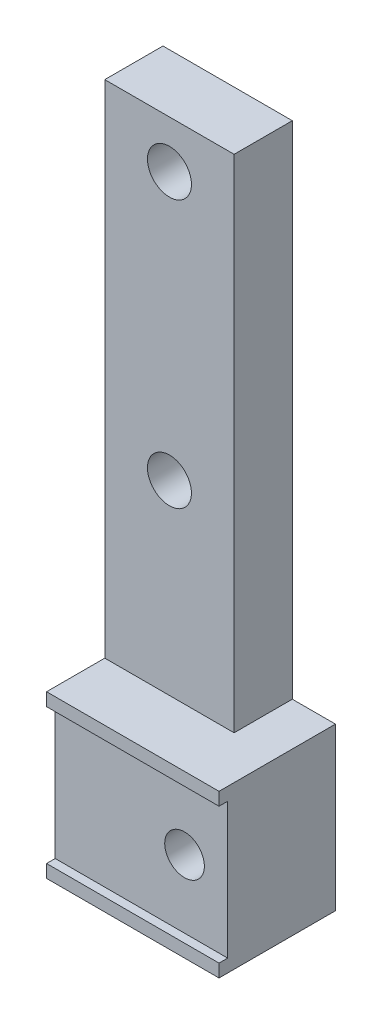
SolidWorks part; units mm, degrees
ref_plane "Front Plane" through (0, 0, 0) normal (0, 0, 1) x (1, 0, 0)
ref_plane "Top Plane" through (0, 0, 0) normal (0, 1, 0) x (1, 0, 0)
ref_plane "Right Plane" through (0, 0, 0) normal (1, 0, 0) x (0, 0, -1)
sketch "ProfileSketch3" plane through (0, 0, 0) normal (0, 0, 1) x (1, 0, 0)
  line L1 (0, 0) -> (20, 0)
  line L2 (0, 0) -> (0, 76.85)
  line L4 (20, 0) -> (20, 18.75)
  line L8 (0, 76.85) -> (15, 76.85)
  line L9 (15, 76.85) -> (15, 18.75)
  line L10 (15, 18.75) -> (20, 18.75)
  circle A0 centre (7.5, 40.35) radius 2.55
  circle A1 centre (7.5, 71.35) radius 2.55
  circle A3 centre (15, 9.375) radius 2.3
  dimension "D8" = 5.1
  dimension "D12" = 4.6
  dimension "D6" = 20
  dimension "D5" = 5.5
  dimension "D3" = 31
  dimension "D13" = 5
  dimension "D15" = 9.375
  dimension "D2" = 7.5
  dimension "D4" = 76.85
  dimension "D7" = 15
  dimension "D9" = 18.75
extrude "ProfileBoss-Extrude1" add sketch "ProfileSketch3" along normal blind 13.5
sketch "Sketch1" plane through (0, 0, 13.5) normal (0, 0, 1) x (1, 0, 0)
  line L0 (0, 76.85) -> (0, 0) construction
  line L1 (0, 1.5) -> (20, 1.5)
  line L2 (0, 1.5) -> (0, 17.25)
  line L3 (0, 17.25) -> (20, 17.25)
  line L4 (20, 1.5) -> (20, 17.25)
  line L5 (20, 0) -> (20, 18.75) construction
  line L6 (0, 0) -> (20, 0) construction
  dimension "D1" = 1.5
  dimension "D2" = 15.75
  dimension "D3" = 7.875
  dimension "D4" = 7.875
extrude "SlidingMountCut-Extrude1" cut sketch "Sketch1" against normal blind 1
sketch "Sketch2" plane through (0, 0, 13.5) normal (0, 0, 1) x (1, 0, 0)
  line L1 (0, 76.85) -> (15, 76.85)
  line L2 (0, 76.85) -> (0, 18.75)
  line L3 (0, 18.75) -> (15, 18.75)
  line L4 (15, 76.85) -> (15, 18.75)
extrude "Cut-Extrude1" cut sketch "Sketch2" against normal blind 6.75
equation "\"SK8RodShaftSupportHeight\"= 42mm"
equation "\"SK8RodShaftSupportLength\"= 15mm"
equation "\"SK8MountHoleDiameter\"= 5mm + .1mm'Add .1mm for printing"
equation "\"SK8RiserWidth\"= 6.75mm'Measured to meet Nema17 Mount Hole Center axis"
equation "\"SK8MountHoleFromSide\"= \"SK8RodShaftSupportLength\" / 2"
equation "\"SK8MountHoleFromEitherEnd\"= 5.5mm"
equation "\"MicroSwitchCutOutLength\"= 13.05mm"
equation "\"MicroSwitchHeight\"= 6.55mm"
equation "\"MicroSwitchMountingHoleOffsetFromSide\"= 3.35mm"
equation "\"MicroSwitchTerminalHeight\"= 3.5mm"
equation "\"MicroSwitchExtraMountingHeight\"= 2mm"
equation "\"MicroSwitchDepth\"= 2.8mm"
equation "\"MicroSwitchMountingHoleOffsetFromBottom\"= 7mm"
equation "\"M2HeatInsertHoleDiameter\"= 3mm + .1mm'Add .1mm for printing"
equation "\"M2HeatInsertHoleDepth\"= 3.1mm'Spec"
equation "\"D1@ProfileBoss-Extrude1\"=\"YAxisHolderThickness\" * 2"
equation "\"MicroSwitchCutOutHeight\"= \"MicroSwitchExtraMountingHeight\" + \"MicroSwitchTerminalHeight\" + \"MicroSwitchHeight\""
equation "\"EndStopCableWidth\"= 3.75mm"
equation "\"EndStopCableDepth\"= 1.75mm"
equation "\"D6@ProfileSketch3\"= \"YEndStopHolderLength\""
equation "\"D5@ProfileSketch3\"=\"SK8MountHoleFromEitherEnd\""
equation "\"D8@ProfileSketch3\"=\"SK8MountHoleDiameter\""
equation "\"Nema17StepperMountSlotDistance\"=31"
equation "\"D3@ProfileSketch3\"=\"Nema17StepperMountSlotDistance\""
equation "\"M3HeatInsertDiameter\"=4.6"
equation "\"YAxisHolderThickness\"= \"SK8RiserWidth\""
equation "\"YEndStopHolderLength\"= \"SK8RodShaftSupportLength\" + \"YEndStopBaseExtraLength\""
equation "\"YEndStopBaseExtraLength\"= 5mm"
equation "\"M3HeatInsertHoleDepth\"= 5.5mm"
equation "\"YAxisEndStopMicroSwitchHolderHeight\"= 18.75'Same as XAxisMircoSwitchHolder"
equation "\"YAxisEndStopMicroSwitchHolderWidth\"= 29.05mm'Same as XAxisMicroSwitchHolder"
equation "\"D12@ProfileSketch3\"=\"M3HeatInsertDiameter\""
equation "\"D15@ProfileSketch3\"=\"YAxisEndStopMicroSwitchHolderHeight\"/2"
equation "\"D2@Sketch1\"=\"YAxisEndStopMicroSwitchHolderHeight\" -\"EndStopSlidingMountWallWidth\" *2"
equation "\"EndStopSlidingMountWallWidth\"= 1.5mm"
equation "\"D1@Sketch1\"=\"EndStopSlidingMountWallWidth\""
equation "\"EndStopSlidingMountDepth\"= 1mm"
equation "\"D1@SlidingMountCut-Extrude1\" = \"EndStopSlidingMountDepth\""
equation "\"EndStopSlidingMountWallPrintOffset\"= .05mm"
equation "\"D2@ProfileSketch3\"=\"SK8RodShaftSupportLength\"/2"
equation "\"D7@ProfileSketch3\"=\"SK8RodShaftSupportLength\""
equation "\"D9@ProfileSketch3\"=\"YAxisEndStopMicroSwitchHolderHeight\""
equation "\"D1@Cut-Extrude1\"=\"YAxisHolderThickness\""
